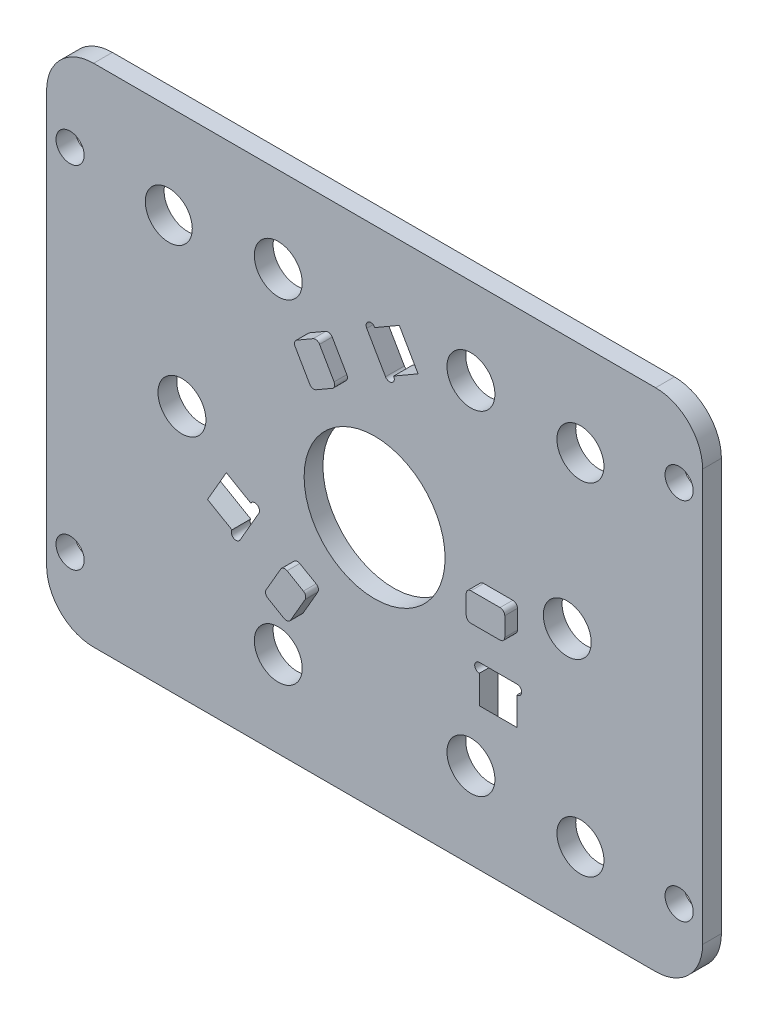
SolidWorks part; units mm, degrees
note: The reader was unsure of these and kept them because the rebuilt part matched: shared geometry of "草圖1<3>".
ref_plane "前基準面" through (0, 0, 0) normal (0, 0, 1) x (1, 0, 0)
ref_plane "上基準面" through (0, 0, 0) normal (0, 1, 0) x (1, 0, 0)
ref_plane "右基準面" through (0, 0, 0) normal (1, 0, 0) x (0, 0, -1)
sketch "草圖1" plane through (0, 0, 0) normal (0, 0, 1) x (1, 0, 0)
  line L0 (17.0528, 0) -> (0, 0) construction
  line L1 (-38, 30) -> (38, 30)
  line L2 (-38, 30) -> (-38, -30)
  line L3 (-38, -30) -> (38, -30)
  line L4 (38, 30) -> (38, -30)
  line L5 (-38, 30) -> (38, -30) construction
  line L6 (-38, -30) -> (38, 30) construction
  line L7 (14.7, -0.2805) -> (11.6, -0.2805)
  line L8 (11.1, -0.7805) -> (11.1, -2.7805)
  line L9 (11.6, -3.2805) -> (14.7, -3.2805)
  line L10 (15.2, -2.7805) -> (15.2, -0.7805)
  line L11 (13.15, -0.2805) -> (13.15, -3.2805) construction
  line L12 (15.2, -1.7805) -> (11.1, -1.7805) construction
  line L13 (13.15, -1.7805) -> (15.2, -0.2805) construction
  line L34 (0, 0) -> (-9.8469, 17.0554) construction
  line L35 (-6.575, 11.3882) -> (13.3346, 22.8831) construction
  line L36 (-7.1071, 12.8708) -> (-5.5571, 10.1861)
  line L41 (-6.9241, 13.5538) -> (-5.192, 14.5538)
  line L42 (-4.509, 14.3708) -> (-2.959, 11.6861)
  line L43 (-3.142, 11.0031) -> (-4.8741, 10.0031)
  line L44 (13.15, -1.7805) -> (13.15, -13.7805) construction
  line L45 (11.15, -7.7805) -> (15.15, -7.7805)
  line L46 (15.15, -7.7805) -> (15.15, -8.7805)
  line L47 (15.15, -8.7805) -> (11.15, -8.7805)
  line L48 (11.15, -8.7805) -> (11.15, -7.7805)
  line L49 (11.15, -8.2805) -> (15.15, -8.2805) construction
  line L50 (-6.0581, 14.0538) -> (-4.0081, 10.5031) construction
  line L55 (-4.759, 14.8038) -> (-5.3071, 9.7531) construction
  line L56 (-7.3571, 13.3038) -> (-2.709, 11.2531) construction
  line L57 (-0.8369, 17.0105) -> (1.1631, 13.5464)
  line L59 (-0.8369, 17.0105) -> (0.0291, 17.5105)
  line L60 (0.0291, 17.5105) -> (2.0291, 14.0464)
  line L61 (2.0291, 14.0464) -> (1.1631, 13.5464)
  line L62 (-0.4039, 17.2605) -> (1.5961, 13.7964) construction
  line L63 (0, 0) -> (-13.9587, -24.1771) construction
  line L64 (-6.575, -11.3882) -> (-27.8389, 0.8885) construction
  line L65 (-6.0429, -9.9057) -> (-7.5929, -12.5903)
  line L66 (-6.2259, -9.2226) -> (-7.958, -8.2226)
  line L67 (-8.641, -8.4057) -> (-10.191, -11.0903)
  line L68 (-10.008, -11.7733) -> (-8.2759, -12.7733)
  line L69 (-7.0919, -8.7226) -> (-9.1419, -12.2733) construction
  line L70 (-8.391, -7.9726) -> (-7.8429, -13.0233) construction
  line L71 (-5.7929, -9.4726) -> (-10.441, -11.5233) construction
  line L72 (-12.3131, -5.7659) -> (-14.3131, -9.23)
  line L73 (-12.3131, -5.7659) -> (-13.1791, -5.2659)
  line L74 (-13.1791, -5.2659) -> (-15.1791, -8.73)
  line L75 (-15.1791, -8.73) -> (-14.3131, -9.23)
  line L76 (-12.7461, -5.5159) -> (-14.7461, -8.98) construction
  circle A4 centre (13.15, -0.9905) radius 0.15 construction
  circle A32 centre (11.15, -8.2805) radius 0.5
  circle A33 centre (15.15, -8.2805) radius 0.5
  circle A36 centre (-0.4039, 17.2605) radius 0.5
  circle A37 centre (1.5961, 13.7964) radius 0.5
  circle A42 centre (-12.7461, -5.5159) radius 0.5
  circle A43 centre (-14.7461, -8.98) radius 0.5
  arc A44 (-7.5929, -12.5903) -> (-8.2759, -12.7733) centre (-8.0259, -12.3403) cw
  arc A45 (-10.191, -11.0903) -> (-10.008, -11.7733) centre (-9.758, -11.3403) ccw
  arc A46 (-6.0429, -9.9057) -> (-6.2259, -9.2226) centre (-6.4759, -9.6557) ccw
  arc A47 (-7.958, -8.2226) -> (-8.641, -8.4057) centre (-8.208, -8.6557) ccw
  arc A48 (-7.1071, 12.8708) -> (-6.9241, 13.5538) centre (-6.6741, 13.1208) cw
  arc A49 (-5.192, 14.5538) -> (-4.509, 14.3708) centre (-4.942, 14.1208) cw
  arc A50 (-2.959, 11.6861) -> (-3.142, 11.0031) centre (-3.392, 11.4361) cw
  arc A51 (-5.5571, 10.1861) -> (-4.8741, 10.0031) centre (-5.1241, 10.4361) ccw
  arc A52 (14.7, -0.2805) -> (15.2, -0.7805) centre (14.7, -0.7805) cw
  arc A53 (14.7, -3.2805) -> (15.2, -2.7805) centre (14.7, -2.7805) ccw
  arc A54 (11.1, -2.7805) -> (11.6, -3.2805) centre (11.6, -2.7805) ccw
  arc A55 (11.6, -0.2805) -> (11.1, -0.7805) centre (11.6, -0.7805) ccw
  point P0 (0, 0)
  point P33 (-6.3321, 11.5285)
  point P48 (0.1631, 15.2785)
  point P60 (-6.8179, -11.248)
  point P74 (13.15, -7.7805)
  point P84 (-13.3131, -7.498)
  point P98 (11.1, -3.2805)
  point P101 (11.1, -0.2805)
  dimension "D5" = 0.561
  dimension "D6" = 0.3
  dimension "D11" = 13.15
  dimension "D22" = 120
  dimension "D17" = 0.561
  dimension "D19" = 4
  dimension "D26" = 0.5
  dimension "D28" = 4
  dimension "D18" = 0.561
  dimension "D1" = 76
  dimension "D2" = 60
  dimension "D3" = 4.1
  dimension "D4" = 3
  dimension "D7" = 0.79
  dimension "D8" = 17.0528
  dimension "D9" = 13.15
  dimension "D10" = 120
  dimension "D12" = 4.1
  dimension "D13" = 4
  dimension "D14" = 1
  dimension "D15" = 5
  dimension "D16" = 3
  dimension "D20" = 1
  dimension "D21" = 5
  dimension "D23" = 13.15
  dimension "D24" = 4.1
  dimension "D25" = 3
  dimension "D29" = 1
  dimension "D30" = 5
extrude "填料-伸長1" add sketch "草圖1" along normal blind 2
extrude "填料-伸長2" add sketch "草圖1<3>" along normal blind 3.35
sketch "草圖1<3>" plane through (0, 0, 0) normal (0, 0, 1) x (1, 0, 0) same geometry as "草圖1"
sketch "草圖2" plane through (0, 0, 0) normal (0, 0, -1) x (-1, 0, 0)
  line L0 (-29.9, 26.9043) -> (29.9, 26.9043)
  line L1 (34.9, 21.9043) -> (34.9, -21.9)
  line L2 (29.9, -26.9) -> (-29.9, -26.9)
  line L3 (-34.9, -21.9) -> (-34.9, 21.9043)
  line L4 (38, 30) -> (-38, 30) construction
  line L5 (-38, 30) -> (-38, -30) construction
  line L6 (38, -30) -> (-38, -30) construction
  line L7 (38, 30) -> (38, -30) construction
  arc A0 (-29.9, -26.9) -> (-34.9, -21.9) centre (-29.9, -21.9) cw
  arc A1 (34.9, -21.9) -> (29.9, -26.9) centre (29.9, -21.9) cw
  arc A2 (29.9, 26.9043) -> (34.9, 21.9043) centre (29.9, 21.9043) cw
  arc A3 (-29.9, 26.9043) -> (-34.9, 21.9043) centre (-29.9, 21.9043) ccw
  line M5 (-38, 30) -> (-38, -30)
  line M6 (-38, -30) -> (38, -30)
  line M7 (38, -30) -> (38, 30)
  line M8 (38, 30) -> (-38, 30)
  dimension "D5" = 5
  dimension "D1" = 3.1
  dimension "D2" = 3.0957
  dimension "D3" = 3.1
  dimension "D4" = 3.1
extrude "除料-伸長1" cut sketch "草圖2" against normal blind 2.95 contours A3 L0 A2 L1 A1 L2 A0 L3 M8 M5 M6 M7
sketch "草圖3" plane through (0, 0, 0) normal (0, 0, -1) x (-1, 0, 0)
  circle A0 centre (20.5, 0) radius 2.55
  circle A3 centre (-20.5, 0) radius 2.55
  circle A6 centre (-10.25, -17.7535) radius 2.55
  circle A7 centre (-10.25, 17.7535) radius 2.55
  circle A8 centre (10.25, 17.7535) radius 2.55
  circle A9 centre (10.25, -17.7535) radius 2.55
  point P9 (0, 0)
  point P12 (0, 0)
  point P17 (0, 0)
  dimension "D1" = 5.1
  dimension "D3" = 5.1
  dimension "D2" = 20.5
  dimension "D4" = 20.5
  dimension "D5" = 3
  dimension "D6" = 3
extrude "除料-伸長2" cut sketch "草圖3" against normal through all
sketch "草圖4" plane through (0, 0, 0) normal (0, 0, -1) x (-1, 0, 0)
  circle A0 centre (0, 0) radius 7.5
  dimension "D1" = 15
extrude "除料-伸長3" cut sketch "草圖4" against normal through all
ref_plane "平面1" through (0, 0, 0) normal (0, 0, -1) x (-1, 0, 0)
sketch "草圖5" plane through (0, 0, 0) normal (0, 0, -1) x (-1, 0, 0)
  line L0 (-34.9, 21.9043) -> (-24.9, 21.9043) construction
  line L1 (-24.9, 21.9043) -> (-24.9, -21.9) construction
  line L2 (-24.9, -21.9) -> (-34.9, -21.9) construction
  line L3 (-34.9, -21.9) -> (-34.9, 21.9043) construction
  line L4 (0, 0) -> (-34.9, 0.0022) construction
  line L5 (0, 26.9043) -> (0, -26.9) construction
  line L6 (-29.9, 26.9043) -> (29.9, 26.9043) construction
  line L7 (29.9, -26.9) -> (-29.9, -26.9) construction
  circle A0 centre (-32.4, 19.4043) radius 1.5
  circle A1 centre (-32.4024, -19.4003) radius 1.5
  circle A2 centre (32.4024, -19.4003) radius 1.5
  circle A3 centre (32.4024, 17.9043) radius 1.5
  dimension "D2" = 3
  dimension "D5" = 3
  dimension "D1" = 10
  dimension "D3" = 2.5
  dimension "D4" = 2.5
  dimension "D6" = 4
extrude "除料-伸長4" cut sketch "草圖5" against normal through all
sketch "草圖6" plane through (0, 0, 0) normal (0, 0, -1) x (-1, 0, 0)
  line L0 (-29.9, 26.9043) -> (29.9, 26.9043) construction
  line L1 (-34.9, -21.9) -> (-34.9, 21.9043) construction
  line L2 (0, 26.9043) -> (0, -26.9) construction
  line L3 (29.9, -26.9) -> (-29.9, -26.9) construction
  circle A0 centre (-21.9, 16.9043) radius 2.5
  circle A1 centre (21.9, 16.9043) radius 2.5
  circle A2 centre (-21.9, -19.4) radius 2.5
  dimension "D3" = 5
  dimension "D4" = 5
  dimension "D1" = 10
  dimension "D2" = 13
  dimension "D5" = 7.5
extrude "除料-伸長5" cut sketch "草圖6" against normal through all
ref_plane "平面2" through (11.15, 0, 0) normal (-1, 0, 0) x (0, 0, 1)
sketch "草圖7" plane through (11.15, 0, 0) normal (-1, 0, 0) x (0, 0, 1)
  line L7 (2, -8.7805) -> (0, -8.7805)
  line L8 (0, 29.5924) -> (0, -29.5924) construction
  line L9 (2, -8.7805) -> (0, -8.7805) construction
  line L10 (0, -8.7805) -> (0, -13.7805)
  line L11 (0, -13.7805) -> (2, -11.7805)
  line L12 (2, 21.9043) -> (2, -21.9) construction
  line L13 (2, -11.7805) -> (2, -8.7805)
  dimension "D1" = 3
  dimension "D2" = 5
extrude "除料-伸長6" cut sketch "草圖7" against normal blind 4
ref_plane "平面3" through (-5.575, 9.6562, 0) normal (0.5, -0.866, 0) x (-0.866, -0.5, 0)
sketch "草圖8" plane through (-5.575, 9.6562, 0) normal (0.5, -0.866, 0) x (-0.866, -0.5, 0)
  line L4 (-7.7805, 0) -> (-8.7805, 0)
  line L5 (-8.7805, 0) -> (-8.7805, -2)
  line L6 (-8.7805, -2) -> (-7.7805, -2)
  line L7 (-7.7805, -2) -> (-7.7805, 0)
  line L8 (-7.7805, 0) -> (-8.7805, 0) construction
  line L9 (-8.7805, 0) -> (-8.7805, -2) construction
  line L10 (-8.7805, -2) -> (-7.7805, -2) construction
  line L11 (-7.7805, -2) -> (-7.7805, 0) construction
  line L16 (-8.7805, -2) -> (-8.7805, 0)
  line L17 (-8.7805, 0) -> (-13.7805, 0)
  line L18 (29.5924, 0) -> (-29.5924, 0) construction
  line L19 (-13.7805, 0) -> (-11.7805, -2)
  line L20 (12.442, -2) -> (-39.3463, -2) construction
  line L21 (-11.7805, -2) -> (-8.7805, -2)
  dimension "D2" = 3
  dimension "D3" = 5
  dimension "D1" = 0
extrude "除料-伸長7" cut sketch "草圖8" against normal blind 4
ref_plane "平面4" through (-5.575, -9.6562, 0) normal (0.5, 0.866, 0) x (0.866, -0.5, 0)
sketch "草圖9" plane through (-5.575, -9.6562, 0) normal (0.5, 0.866, 0) x (0.866, -0.5, 0)
  line L7 (-8.7805, -2) -> (-8.7805, 0)
  line L8 (29.5924, 0) -> (-29.5924, 0) construction
  line L9 (-8.7805, -2) -> (-8.7805, 0) construction
  line L10 (-8.7805, 0) -> (-13.7805, 0)
  line L11 (-13.7805, 0) -> (-11.7805, -2)
  line L12 (-19.2743, -2) -> (-12.4442, -2) construction
  line L13 (-11.7805, -2) -> (-8.7805, -2)
  dimension "D1" = 3
  dimension "D2" = 5
extrude "除料-伸長8" cut sketch "草圖9" against normal blind 4
